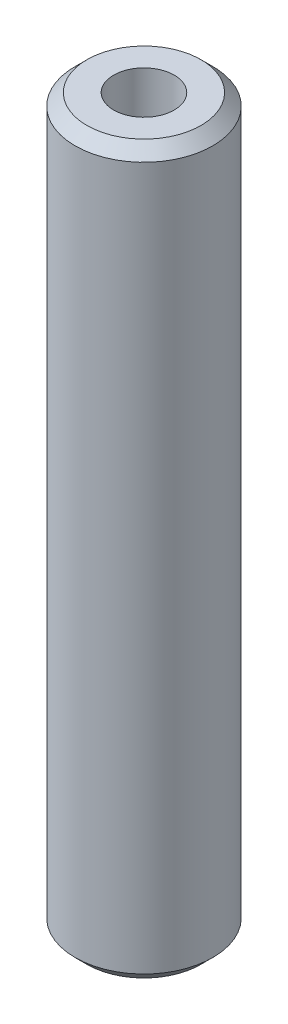
SolidWorks part; units mm, degrees
ref_plane "Front Plane" through (0, 0, 0) normal (0, 0, 1) x (1, 0, 0)
ref_plane "Top Plane" through (0, 0, 0) normal (0, 1, 0) x (1, 0, 0)
ref_plane "Right Plane" through (0, 0, 0) normal (1, 0, 0) x (0, 0, -1)
sketch "Sketch1" plane through (0, 0, 0) normal (0, 1, 0) x (1, 0, 0)
  circle A0 centre (0, 0) radius 5
  dimension "SHAFT_OD" = 10
extrude "Boss-Extrude1" add sketch "Sketch1" along normal blind 52.7983
sketch "Sketch2" plane through (0, 0, 0) normal (0, 1, 0) x (1, 0, 0)
  circle A0 centre (0, 0) radius 2.2004
  dimension "BORE_D" = 4.4008
extrude "Cut-Extrude1" cut sketch "Sketch2" along normal through all
chamfer "Chamfer1" distance 0.8548 angle 45 2 edges at (0, 52.7983, 5) (0, 0, 5)
